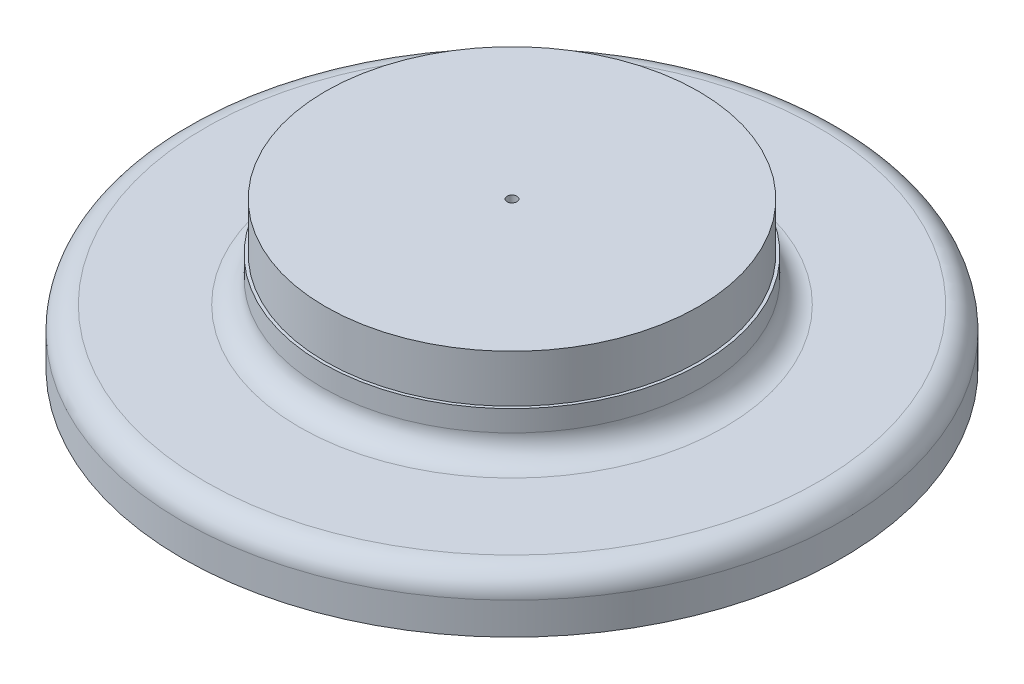
SolidWorks part; units mm, degrees
ref_plane "Front Plane" through (0, 0, 0) normal (0, 0, 1) x (1, 0, 0)
ref_plane "Top Plane" through (0, 0, 0) normal (0, 1, 0) x (1, 0, 0)
ref_plane "Right Plane" through (0, 0, 0) normal (1, 0, 0) x (0, 0, -1)
sketch "Sketch1" plane through (0, 0, 0) normal (0, 1, 0) x (1, 0, 0)
  circle A0 centre (0, 0) radius 129.413
  circle A1 centre (0, 0) radius 131.445
  circle A2 centre (0, 0) radius 228.6
extrude "Boss-Extrude1" add sketch "Sketch1" along normal blind 38.1 contours A2 A1 region at (-222.1342, 0, 0)
extrude "Boss-Extrude2" add sketch "Sketch1<3>" along normal blind 68.58 contours A1 A0 region at (-131.0732, 0, 0)
sketch "Sketch1<3>" plane through (0, 0, 0) normal (0, 1, 0) x (1, 0, 0) same geometry as "Sketch1"
extrude "Boss-Extrude3" add sketch "Sketch1<4>" along normal blind 101.6 contours A0 region at (0, 0, 0)
sketch "Sketch1<4>" plane through (0, 0, 0) normal (0, 1, 0) x (1, 0, 0) same geometry as "Sketch1"
hole_wizard "CSK for 1/4 Flat Head Machine Screw (100)1" positions "Sketch2" profile "Sketch3" countersink size "1/4" standard "ANSI Inch" end condition through all
sketch "Sketch2" plane through (0, 0, 0) normal (0, -1, 0) x (-1, 0, 0)
  point P0 (0, 0)
sketch "Sketch3" plane through (0, 0, 0) normal (1, 0, 0) x (0, 0, -1)
  line L0 (0, 0) -> (0, 101.6)
  line L1 (0, 101.6) -> (3.3782, 101.6)
  line L2 (3.3782, 101.6) -> (3.3782, 2.5682)
  line L3 (3.3782, 2.5682) -> (6.4389, 0)
  line L5 (6.4389, 0) -> (0, 0)
  line L6 (-3.3782, 2.5682) -> (-6.4389, 0) construction
  line L11 (0, -6.35) -> (0, 107.95) construction
  dimension "Thru Hole Dia." = 6.7564
  dimension "Thru Hole Depth" = 101.6
  dimension "Near C'Sink Dia." = 12.8778
  dimension "Near C'Sink Angle" = 100
fillet "Fillet1" radius 15.875 1 edges at (0, 38.1, 131.445)
fillet "Fillet2" radius 15.875 1 edges at (0, 38.1, 228.6)
